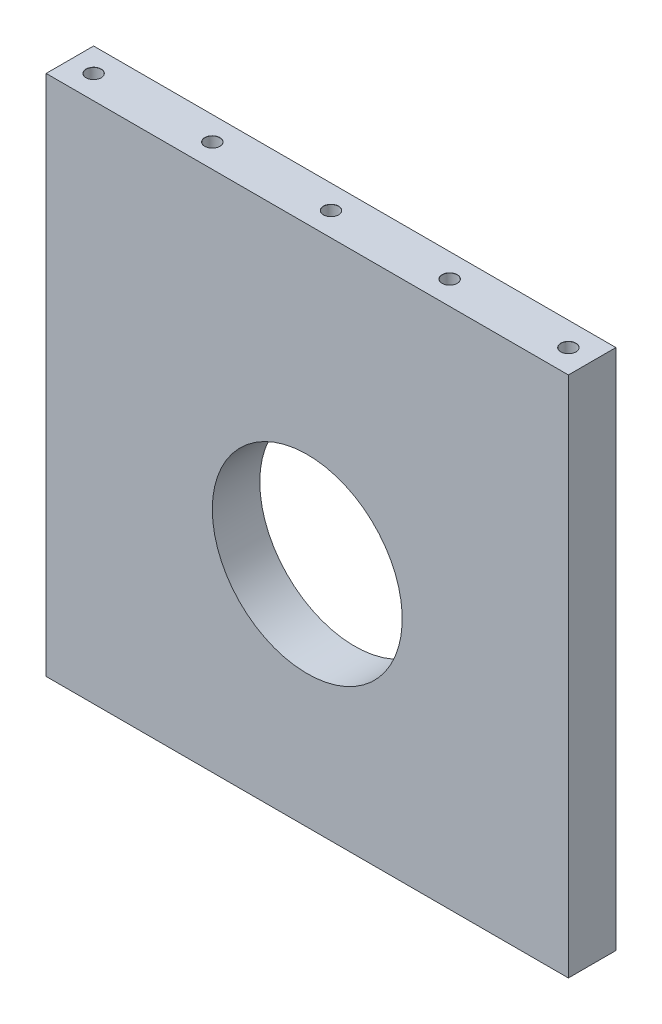
SolidWorks part; units mm, degrees
material "6061-T6 (SS)"
ref_plane "Front Plane" through (0, 0, 0) normal (0, 0, 1) x (1, 0, 0)
ref_plane "Top Plane" through (0, 0, 0) normal (0, 1, 0) x (1, 0, 0)
ref_plane "Right Plane" through (0, 0, 0) normal (1, 0, 0) x (0, 0, -1)
sketch "Sketch1" plane through (0, 0, 0) normal (0, 0, 1) x (1, 0, 0)
  line L1 (0, 0) -> (110, 0)
  line L2 (0, 0) -> (0, 110)
  line L3 (0, 110) -> (110, 110)
  line L4 (110, 0) -> (110, 110)
  dimension "D1" = 110
  dimension "D2" = 110
extrude "Boss-Extrude1" add sketch "Sketch1" along normal blind 10
sketch "Sketch2" plane through (0, 110, 0) normal (0, 1, 0) x (1, 0, 0)
  line L0 (0, -5) -> (110, -5) construction
  line L1 (0, -10) -> (0, 0) construction
  line L2 (110, -10) -> (110, 0) construction
  point P9 (55, -5)
  point P18 (80, -5)
  point P19 (105, -5)
  point P20 (55, -5)
  point P21 (80, -5)
  point P22 (30, -5)
  point P23 (55, -5)
  point P24 (30, -5)
  point P25 (5, -5)
  dimension "D1" = 3
  dimension "D2" = 3
hole_wizard "Tap Drill for M3 Helicoil1" positions "Sketch2" profile "Sketch4" hole size "M3x0.5" standard "DIN"
sketch "Sketch4" plane through (5, 110, 5) normal (1, 0, 0) x (0, 0, 1)
  line L0 (0, 0) -> (0, 6.9464)
  line L1 (0, 6.9464) -> (1.575, 6)
  line L2 (1.575, 6) -> (1.575, 0.025)
  line L3 (1.575, 0.025) -> (1.6, 0)
  line L5 (1.6, 0) -> (0, 0)
  line L6 (-1.575, 0.025) -> (-1.6, 0) construction
  line L10 (0, 6.9464) -> (-1.575, 6) construction
  line L11 (0, -6.35) -> (0, 107.95) construction
  dimension "Hole Dia." = 3.15
  dimension "Hole Depth" = 6
  dimension "Near C'Sink Dia." = 3.2
  dimension "Near C'Sink Angle" = 90
  dimension "Drill Angle" = 118
sketch "Sketch5" plane through (0, 0, 0) normal (0, 0, -1) x (-1, 0, 0)
  circle A0 centre (-55, 48) radius 40 construction
  point P8 (-55, 48)
hole_wizard "Ø40.0 (40) Diameter Hole1" positions "Sketch5" profile "Sketch7" hole size "Ø40.0" standard "DIN" end condition through all
sketch "Sketch7" plane through (55, 48, 0) normal (1, 0, 0) x (0, 1, 0)
  line L0 (0, 0) -> (0, 10)
  line L1 (0, 10) -> (20, 10)
  line L2 (20, 10) -> (20, 0)
  line L5 (20, 0) -> (0, 0)
  line L11 (0, -6.35) -> (0, 107.95) construction
  dimension "Thru Hole Dia." = 40
  dimension "Thru Hole Depth" = 10
